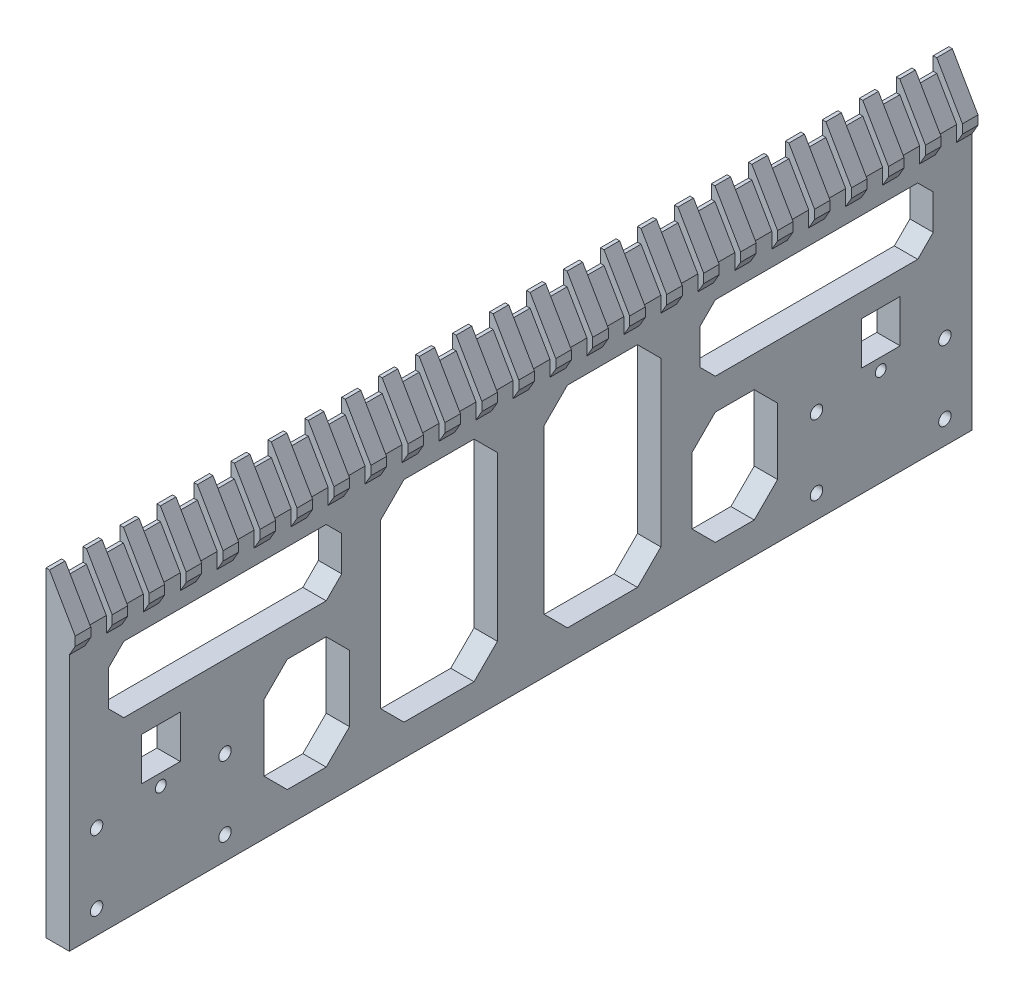
SolidWorks part; units mm, degrees
ref_plane "前视基准面" through (0, 0, 0) normal (0, 0, 1) x (1, 0, 0)
ref_plane "上视基准面" through (0, 0, 0) normal (0, 1, 0) x (1, 0, 0)
ref_plane "右视基准面" through (0, 0, 0) normal (1, 0, 0) x (0, 0, -1)
sketch "草图1" plane through (0, 0, 0) normal (1, 0, 0) x (0, 0, -1)
  line L0 (0, 0) -> (0, -70) construction
  line L1 (-116, 0) -> (116, 0)
  line L2 (-116, 0) -> (-116, -70)
  line L3 (-116, -70) -> (116, -70)
  line L4 (116, 0) -> (116, -70)
  point P5 (0, 0)
  dimension "D1" = 116
  dimension "D2" = 70
extrude "凸台-拉伸1" add sketch "草图1" along normal blind 6
sketch "草图3" plane through (6, 0, 0) normal (1, 0, 0) x (0, 0, -1)
  line L0 (0, 0) -> (0, -70) construction
  line L1 (-102, -8) -> (-50, -8)
  line L2 (-106, -12) -> (-106, -21)
  line L3 (-102, -25) -> (-50, -25)
  line L4 (-46, -12) -> (-46, -21)
  line L5 (116, 0) -> (-116, 0) construction
  line L6 (-116, -70) -> (116, -70) construction
  line L7 (-116, 0) -> (-116, -70) construction
  line L12 (-106, -12) -> (-102, -8)
  line L13 (-106, -21) -> (-102, -25)
  line L14 (-50, -25) -> (-46, -21)
  line L15 (-50, -8) -> (-46, -12)
  line L28 (-36, -14) -> (-30, -8)
  line L36 (-66, -56) -> (-60, -62)
  line L42 (-30, -8) -> (-12, -8)
  line L43 (-36, -14) -> (-36, -56)
  line L44 (-30, -62) -> (-12, -62)
  line L45 (-6, -14) -> (-6, -56)
  line L46 (-12, -8) -> (-6, -14)
  line L47 (-12, -62) -> (-6, -56)
  line L48 (-36, -56) -> (-30, -62)
  line L49 (-60, -33) -> (-50, -33)
  line L50 (-66, -39) -> (-66, -56)
  line L51 (-60, -62) -> (-50, -62)
  line L52 (-44, -39) -> (-44, -56)
  line L53 (-50, -62) -> (-44, -56)
  line L54 (-50, -33) -> (-44, -39)
  line L55 (-66, -39) -> (-60, -33)
  point P0 (-106, -8)
  point P1 (-46, -25)
  point P2 (-106, -25)
  point P3 (-46, -8)
  point P20 (-36, -8)
  point P21 (-6, -62)
  point P22 (-36, -62)
  point P23 (-6, -8)
  point P24 (-66, -33)
  point P33 (-44, -62)
  point P34 (-66, -62)
  point P35 (-44, -33)
  dimension "D1" = 10
  dimension "D2" = 8
  dimension "D3" = 17
  dimension "D4" = 60
  dimension "D5" = 8
  dimension "D6" = 8
  dimension "D7" = 54
  dimension "D12" = 80
  dimension "D13" = 6
  dimension "D14" = 30
  dimension "D15" = 10
  dimension "D16" = 8
  dimension "D21" = 8
  dimension "D22" = 29
  dimension "D23" = 22
extrude "切除-拉伸2" cut sketch "草图3" against normal through all
sketch "草图2" plane through (0, 0, 0) normal (1, 0, 0) x (0, 0, -1)
  line L0 (-92.5, -26.6289) -> (-92.5, -71.7155) construction
  line L1 (-109, -46) -> (-76, -46) construction
  line L2 (-109, -46) -> (-109, -64) construction
  line L3 (-109, -64) -> (-76, -64) construction
  line L4 (-76, -46) -> (-76, -64) construction
  line L5 (116, 0) -> (-116, 0) construction
  line L6 (0, 0) -> (0, -70) construction
  circle A0 centre (-109, -46) radius 1.55
  circle A1 centre (-76, -64) radius 1.55
  circle A2 centre (-76, -46) radius 1.55
  circle A3 centre (-109, -64) radius 1.55
  point P8 (-92.5, -46)
  point P9 (27, -46)
  point P14 (25.5, -45.9682)
  point P15 (-92.5, -46)
  point P16 (0, 0)
  point P17 (27.5, -46)
  point P19 (27.5, -46)
  point P23 (0, 0)
  dimension "D5" = 3.1
  dimension "D1" = 92.5
  dimension "D2" = 46
  dimension "D3" = 33
  dimension "D4" = 18
sketch "草图6" plane through (0, 0, 116) normal (0, 0, 1) x (1, 0, 0)
  line L0 (6, 0) -> (0, 0)
  line L1 (0, 0) -> (0, 8.8335)
  line L2 (0.9, 8.8335) -> (6, 0)
  line L3 (0, 8.8335) -> (0.9, 8.8335)
  line L4 (0, 8.8335) -> (0, 10.3923) construction
  line L5 (0, 10.3923) -> (0.9, 8.8335) construction
  dimension "D1" = 30
  dimension "D2" = 0.9
extrude "凸台-拉伸2" add sketch "草图6" against normal up to surface (232 mm away) up to face at (3, -35, -116)
ref_plane "基准面1" through (0, 0, 0) normal (0, 0, -1) x (-1, 0, 0)
sketch "草图8" plane through (0, 0, 116) normal (0, 0, 1) x (1, 0, 0)
  line L0 (0, 10.3923) -> (0, 12.3335)
  line L1 (0.9, 12.3335) -> (7.5, 0.9019)
  line L2 (7.5, 0.9019) -> (7.5, -1.4019)
  line L3 (7.5, -4) -> (6, -4) construction
  line L4 (6, 0) -> (6, -70) construction
  line L5 (6, -4) -> (6, 0)
  line L6 (6, 0) -> (0.9, 8.8335) construction
  line L7 (6, 0) -> (0.9, 8.8335)
  line L8 (0, 12.3335) -> (0.9, 12.3335)
  line L9 (0, 12.3335) -> (0, 13.8923) construction
  line L10 (0, 13.8923) -> (0.9, 12.3335) construction
  line L11 (0, 10.3923) -> (0, 8.8335)
  line L12 (0, 8.8335) -> (0.9, 8.8335)
  line L13 (0.9, 8.8335) -> (0, 10.3923) construction
  line L14 (6, -4) -> (7.5, -1.4019)
  line L15 (7.5, -1.4019) -> (7.5, -4) construction
  dimension "D1" = 3.5
  dimension "D2" = 1.5
  dimension "D3" = 4
  dimension "D4" = 0.9
  dimension "D5" = 30
extrude "凸台-拉伸3" add sketch "草图8" against normal blind 4
pattern_linear "阵列(线性)1" count 25 spacing 9.5 along (0, 0, -1) of "凸台-拉伸3"
hole_wizard "打孔尺寸(%根据)内六角圆柱头螺钉的类型1" positions "草图14" profile "草图15" counterbore size "M3" standard "GB" end condition through all
sketch "草图14" plane through (0, 0, 0) normal (-1, 0, 0) x (0, 0, 1)
  point P0 (76, -46)
  point P3 (109, -46)
  point P6 (109, -64)
  point P9 (76, -64)
sketch "草图15" plane through (0, -46, 76) normal (0, 1, 0) x (0, 0, 1)
  line L0 (0, 0) -> (0, 7.5)
  line L1 (0, 7.5) -> (1.6, 7.5)
  line L3 (1.6, 7.5) -> (1.6, 3.4)
  line L4 (1.6, 3.4) -> (3, 3.4)
  line L5 (3, 3.4) -> (3, 0)
  line L7 (3, 0) -> (0, 0)
  line L11 (0, -6.35) -> (0, 107.95) construction
  dimension "通孔孔直径" = 3.2
  dimension "通孔孔深度" = 7.5
  dimension "柱形沉头孔直径" = 6
  dimension "柱形沉头孔深度" = 3.4
sketch "草图16" plane through (0, 0, 0) normal (-1, 0, 0) x (0, 0, 1)
  line L0 (109, -46) -> (76, -46) construction
  line L2 (116, -70) -> (-116, -70) construction
  line L3 (92.5, -26.6289) -> (92.5, -71.7155) construction
  circle A0 centre (92.5, -45) radius 1.4
  point P6 (0, 0)
  point P7 (-23.75, -45)
  dimension "D1" = 2.8
  dimension "D2" = 25
extrude "切除-拉伸3" cut sketch "草图16" against normal blind 10
mirror "镜向1" about plane through (0, 0, 0) normal (0, 0, -1) of "打孔尺寸(%根据)内六角圆柱头螺钉的类型1"
mirror "镜向2" about plane through (0, 0, 0) normal (0, 0, -1) of "切除-拉伸3", "切除-拉伸2"
sketch "草图17" plane through (0, 0, 0) normal (-1, 0, 0) x (0, 0, 1)
  line L1 (87.5, -31) -> (97.5, -31)
  line L2 (87.5, -31) -> (87.5, -42)
  line L3 (87.5, -42) -> (97.5, -42)
  line L4 (97.5, -31) -> (97.5, -42)
  line L6 (116, -70) -> (-116, -70) construction
  line L7 (0, -70) -> (0, -8.018) construction
  line L8 (-87.5, -31) -> (-97.5, -31)
  line L9 (-87.5, -31) -> (-87.5, -42)
  line L10 (-87.5, -42) -> (-97.5, -42)
  line L11 (-97.5, -31) -> (-97.5, -42)
  line L12 (92.5, -26.6289) -> (92.5, -71.7155) construction
  line L13 (92.5, -26.6289) -> (92.5, -71.7155) construction
  point P4 (-27.5, -75.4115)
  dimension "D1" = 10
  dimension "D2" = 11
  dimension "D4" = 28
extrude "切除-拉伸4" cut sketch "草图17" against normal through all
